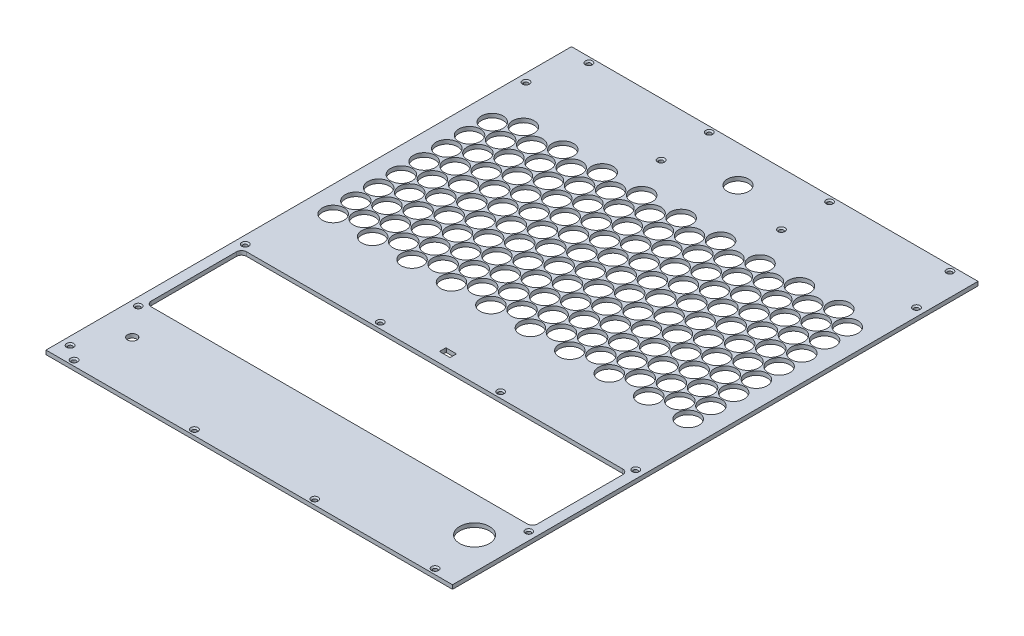
SolidWorks part; units mm, degrees
ref_plane "Ebene vorne" through (0, 0, 0) normal (0, 0, 1) x (1, 0, 0)
ref_plane "Ebene oben" through (0, 0, 0) normal (0, 1, 0) x (1, 0, 0)
ref_plane "Ebene rechts" through (0, 0, 0) normal (1, 0, 0) x (0, 0, -1)
sketch "Skizze1" plane through (0, 0, 0) normal (0, 1, 0) x (1, 0, 0)
  line L1 (-152, 250) -> (152, 250)
  line L2 (-152, 250) -> (-152, -143)
  line L3 (-152, -143) -> (152, -143)
  line L4 (152, 250) -> (152, -143)
  line L5 (-152, 250) -> (152, -143) construction
  line L6 (-152, -143) -> (152, 250) construction
  point P0 (0, 53.5)
  point P6 (0, 0)
extrude "Aufsatz-Linear austragen1" add sketch "Skizze1" along normal blind 3
sketch "Skizze3" plane through (0, 3, 0) normal (0, 1, 0) x (1, 0, 0)
  line L0 (0, 0) -> (0, 250)
  line L1 (152, 250) -> (-152, 250) construction
  circle A0 centre (-146, -131) radius 1.6
  circle A1 centre (-146, -80) radius 1.6
  circle A2 centre (-146, 0) radius 1.6
  circle A3 centre (-146, 210) radius 1.6
  circle A4 centre (-45, 0) radius 1.6
  circle A5 centre (-45, 210) radius 1.6
  circle A6 centre (45, 210) radius 1.6
  circle A7 centre (45, 0) radius 1.6
  circle A8 centre (146, 210) radius 1.6
  circle A9 centre (146, 0) radius 1.6
  circle A10 centre (146, -80) radius 1.6
extrude "PCB-Screws" cut sketch "Skizze3" against normal through all contours A0 | A1 | A2 | A4 | A7 | A9 | A10 | A8 | A6 | A5 | A3 region at (-146, 3, 131) region at (-146, 3, 80) region at (-146, 3, 0) region at (-146, 3, -210) region at (-45, 3, 0) region at (-45, 3, -210) region at (45, 3, -210) region at (45, 3, 0) region at (146, 3, -210) region at (146, 3, 0) region at (146, 3, 80)
sketch "Skizze4" plane through (0, 3, 0) normal (0, 1, 0) x (1, 0, 0)
  circle A0 centre (0, 61) radius 8.075
  circle A1 centre (0, 78) radius 8.075
  circle A2 centre (0, 95) radius 8.075
  circle A3 centre (0, 112) radius 8.075
  circle A4 centre (0, 129) radius 8.075
  circle A5 centre (0, 146) radius 8.075
  circle A6 centre (0, 163) radius 8.075
  circle A7 centre (0, 180) radius 8.075
  circle A8 centre (-14.75, 52.5) radius 8.075
  circle A9 centre (-14.75, 69.5) radius 8.075
  circle A10 centre (-14.75, 86.5) radius 8.075
  circle A11 centre (-14.75, 103.5) radius 8.075
  circle A12 centre (-14.75, 120.5) radius 8.075
  circle A13 centre (-14.75, 137.5) radius 8.075
  circle A14 centre (-14.75, 154.5) radius 8.075
  circle A15 centre (-14.75, 171.5) radius 8.075
  circle A16 centre (-29.5, 61) radius 8.075
  circle A17 centre (-29.5, 78) radius 8.075
  circle A18 centre (-29.5, 95) radius 8.075
  circle A19 centre (-29.5, 112) radius 8.075
  circle A20 centre (-29.5, 129) radius 8.075
  circle A21 centre (-29.5, 146) radius 8.075
  circle A22 centre (-29.5, 163) radius 8.075
  circle A23 centre (-29.5, 180) radius 8.075
  circle A24 centre (-44.25, 52.5) radius 8.075
  circle A25 centre (-44.25, 69.5) radius 8.075
  circle A26 centre (-44.25, 86.5) radius 8.075
  circle A27 centre (-44.25, 103.5) radius 8.075
  circle A28 centre (-44.25, 120.5) radius 8.075
  circle A29 centre (-44.25, 137.5) radius 8.075
  circle A30 centre (-44.25, 154.5) radius 8.075
  circle A31 centre (-44.25, 171.5) radius 8.075
  circle A32 centre (-59, 61) radius 8.075
  circle A33 centre (-59, 78) radius 8.075
  circle A34 centre (-59, 95) radius 8.075
  circle A35 centre (-59, 112) radius 8.075
  circle A36 centre (-59, 129) radius 8.075
  circle A37 centre (-59, 146) radius 8.075
  circle A38 centre (-59, 163) radius 8.075
  circle A39 centre (-59, 180) radius 8.075
  circle A40 centre (-73.75, 52.5) radius 8.075
  circle A41 centre (-73.75, 69.5) radius 8.075
  circle A42 centre (-73.75, 86.5) radius 8.075
  circle A43 centre (-73.75, 103.5) radius 8.075
  circle A44 centre (-73.75, 120.5) radius 8.075
  circle A45 centre (-73.75, 137.5) radius 8.075
  circle A46 centre (-73.75, 154.5) radius 8.075
  circle A47 centre (-73.75, 171.5) radius 8.075
  circle A48 centre (-88.5, 61) radius 8.075
  circle A49 centre (-88.5, 78) radius 8.075
  circle A50 centre (-88.5, 95) radius 8.075
  circle A51 centre (-88.5, 112) radius 8.075
  circle A52 centre (-88.5, 129) radius 8.075
  circle A53 centre (-88.5, 146) radius 8.075
  circle A54 centre (-88.5, 163) radius 8.075
  circle A55 centre (-88.5, 180) radius 8.075
  circle A56 centre (-103.25, 52.5) radius 8.075
  circle A57 centre (-103.25, 69.5) radius 8.075
  circle A58 centre (-103.25, 86.5) radius 8.075
  circle A59 centre (-103.25, 103.5) radius 8.075
  circle A60 centre (-103.25, 120.5) radius 8.075
  circle A61 centre (-103.25, 137.5) radius 8.075
  circle A62 centre (-103.25, 154.5) radius 8.075
  circle A63 centre (-103.25, 171.5) radius 8.075
  circle A64 centre (-118, 61) radius 8.075
  circle A65 centre (-118, 78) radius 8.075
  circle A66 centre (-118, 95) radius 8.075
  circle A67 centre (-118, 112) radius 8.075
  circle A68 centre (-118, 129) radius 8.075
  circle A69 centre (-118, 146) radius 8.075
  circle A70 centre (-118, 163) radius 8.075
  circle A71 centre (-118, 180) radius 8.075
  circle A72 centre (-132.75, 52.5) radius 8.075
  circle A73 centre (-132.75, 69.5) radius 8.075
  circle A74 centre (-132.75, 86.5) radius 8.075
  circle A75 centre (-132.75, 103.5) radius 8.075
  circle A76 centre (-132.75, 120.5) radius 8.075
  circle A77 centre (-132.75, 137.5) radius 8.075
  circle A78 centre (-132.75, 154.5) radius 8.075
  circle A79 centre (-132.75, 171.5) radius 8.075
  circle A80 centre (29.5, 61) radius 8.075
  circle A81 centre (29.5, 78) radius 8.075
  circle A82 centre (29.5, 95) radius 8.075
  circle A83 centre (29.5, 112) radius 8.075
  circle A84 centre (29.5, 129) radius 8.075
  circle A85 centre (29.5, 146) radius 8.075
  circle A86 centre (29.5, 163) radius 8.075
  circle A87 centre (29.5, 180) radius 8.075
  circle A88 centre (14.75, 52.5) radius 8.075
  circle A89 centre (14.75, 69.5) radius 8.075
  circle A90 centre (14.75, 86.5) radius 8.075
  circle A91 centre (14.75, 103.5) radius 8.075
  circle A92 centre (14.75, 120.5) radius 8.075
  circle A93 centre (14.75, 137.5) radius 8.075
  circle A94 centre (14.75, 154.5) radius 8.075
  circle A95 centre (14.75, 171.5) radius 8.075
  circle A96 centre (59, 61) radius 8.075
  circle A97 centre (59, 78) radius 8.075
  circle A98 centre (59, 95) radius 8.075
  circle A99 centre (59, 112) radius 8.075
  circle A100 centre (59, 129) radius 8.075
  circle A101 centre (59, 146) radius 8.075
  circle A102 centre (59, 163) radius 8.075
  circle A103 centre (59, 180) radius 8.075
  circle A104 centre (44.25, 52.5) radius 8.075
  circle A105 centre (44.25, 69.5) radius 8.075
  circle A106 centre (44.25, 86.5) radius 8.075
  circle A107 centre (44.25, 103.5) radius 8.075
  circle A108 centre (44.25, 120.5) radius 8.075
  circle A109 centre (44.25, 137.5) radius 8.075
  circle A110 centre (44.25, 154.5) radius 8.075
  circle A111 centre (44.25, 171.5) radius 8.075
  circle A112 centre (88.5, 61) radius 8.075
  circle A113 centre (88.5, 78) radius 8.075
  circle A114 centre (88.5, 95) radius 8.075
  circle A115 centre (88.5, 112) radius 8.075
  circle A116 centre (88.5, 129) radius 8.075
  circle A117 centre (88.5, 146) radius 8.075
  circle A118 centre (88.5, 163) radius 8.075
  circle A119 centre (88.5, 180) radius 8.075
  circle A120 centre (73.75, 52.5) radius 8.075
  circle A121 centre (73.75, 69.5) radius 8.075
  circle A122 centre (73.75, 86.5) radius 8.075
  circle A123 centre (73.75, 103.5) radius 8.075
  circle A124 centre (73.75, 120.5) radius 8.075
  circle A125 centre (73.75, 137.5) radius 8.075
  circle A126 centre (73.75, 154.5) radius 8.075
  circle A127 centre (73.75, 171.5) radius 8.075
  circle A128 centre (118, 61) radius 8.075
  circle A129 centre (118, 78) radius 8.075
  circle A130 centre (118, 95) radius 8.075
  circle A131 centre (118, 112) radius 8.075
  circle A132 centre (118, 129) radius 8.075
  circle A133 centre (118, 146) radius 8.075
  circle A134 centre (118, 163) radius 8.075
  circle A135 centre (118, 180) radius 8.075
  circle A136 centre (103.25, 52.5) radius 8.075
  circle A137 centre (103.25, 69.5) radius 8.075
  circle A138 centre (103.25, 86.5) radius 8.075
  circle A139 centre (103.25, 103.5) radius 8.075
  circle A140 centre (103.25, 120.5) radius 8.075
  circle A141 centre (103.25, 137.5) radius 8.075
  circle A142 centre (103.25, 154.5) radius 8.075
  circle A143 centre (103.25, 171.5) radius 8.075
  circle A152 centre (132.75, 52.5) radius 8.075
  circle A153 centre (132.75, 69.5) radius 8.075
  circle A154 centre (132.75, 86.5) radius 8.075
  circle A155 centre (132.75, 103.5) radius 8.075
  circle A156 centre (132.75, 120.5) radius 8.075
  circle A157 centre (132.75, 137.5) radius 8.075
  circle A158 centre (132.75, 154.5) radius 8.075
  circle A159 centre (132.75, 171.5) radius 8.075
  circle A160 centre (147.5, 61) radius 8.075 [skipped]
  circle A161 centre (147.5, 78) radius 8.075 [skipped]
  circle A162 centre (147.5, 95) radius 8.075 [skipped]
  circle A163 centre (147.5, 112) radius 8.075 [skipped]
  circle A164 centre (147.5, 129) radius 8.075 [skipped]
  circle A165 centre (147.5, 146) radius 8.075 [skipped]
  circle A166 centre (147.5, 163) radius 8.075 [skipped]
  circle A167 centre (147.5, 180) radius 8.075 [skipped]
  dimension "D1" = 8
  dimension "D2" = 8
extrude "Transducers" cut sketch "Skizze4" against normal through all
sketch "Skizze5" plane through (0, 3, 0) normal (0, 1, 0) x (1, 0, 0)
  line L0 (-3.45, 8.02) -> (3.45, 8.02)
  line L1 (-3.2, 7.27) -> (3.2, 7.27)
  line L2 (-3.2, 7.27) -> (-3.2, 3.97)
  line L3 (-3.2, 3.97) -> (3.2, 3.97)
  line L4 (3.2, 7.27) -> (3.2, 3.97)
  line L5 (-3.2, 7.27) -> (3.2, 3.97) construction
  line L6 (-3.2, 3.97) -> (3.2, 7.27) construction
  line L7 (3.95, 7.52) -> (3.95, 3.72)
  line L8 (-3.45, 3.22) -> (3.45, 3.22)
  line L9 (-3.95, 7.52) -> (-3.95, 3.72)
  line L10 (-3.95, 8.02) -> (3.95, 8.02) construction
  line L11 (3.95, 8.02) -> (3.95, 3.22) construction
  line L12 (-3.95, 3.22) -> (3.95, 3.22) construction
  line L13 (-3.95, 8.02) -> (-3.95, 3.22) construction
  arc A0 (3.45, 8.02) -> (3.95, 7.52) centre (3.45, 7.52) cw
  arc A1 (3.95, 3.72) -> (3.45, 3.22) centre (3.45, 3.72) cw
  arc A2 (-3.45, 3.22) -> (-3.95, 3.72) centre (-3.45, 3.72) cw
  arc A3 (-3.45, 8.02) -> (-3.95, 7.52) centre (-3.45, 7.52) ccw
  point P0 (0, 5.62)
  point P5 (0, 0)
  point P6 (0, 0)
  dimension "D2" = 0.5
  dimension "D1" = 0.75
extrude "ToF-Sensor" cut sketch "Skizze5" against normal through all contours L0 A3 L9 A2 L8 A1 L7 A0 L1 L4 L3 L2 | L4 L1 L2 L3 region at (0, 3, -7.9276) region at (0, 3, -5.62)
sketch "Skizze6" plane through (0, 3, 0) normal (0, 1, 0) x (1, 0, 0)
  line L0 (-144.4, -8.1) -> (-144.4, -71.9)
  line L1 (-140.65, -5.1) -> (140.65, -5.1)
  line L2 (-143.65, -8.1) -> (-143.65, -71.9)
  line L3 (-140.65, -74.9) -> (140.65, -74.9)
  line L4 (143.65, -8.1) -> (143.65, -71.9)
  line L5 (-143.65, -5.1) -> (143.65, -74.9) construction
  line L6 (-143.65, -74.9) -> (143.65, -5.1) construction
  line L7 (-140.65, -75.65) -> (140.65, -75.65)
  line L8 (144.4, -8.1) -> (144.4, -71.9)
  line L9 (-140.65, -4.35) -> (140.65, -4.35)
  arc A0 (140.65, -74.9) -> (143.65, -71.9) centre (140.65, -71.9) ccw
  arc A1 (-143.65, -71.9) -> (-140.65, -74.9) centre (-140.65, -71.9) ccw
  arc A2 (-140.65, -5.1) -> (-143.65, -8.1) centre (-140.65, -8.1) ccw
  arc A3 (140.65, -5.1) -> (143.65, -8.1) centre (140.65, -8.1) cw
  arc A4 (-144.4, -71.9) -> (-140.65, -75.65) centre (-140.65, -71.9) ccw
  arc A5 (140.65, -75.65) -> (144.4, -71.9) centre (140.65, -71.9) ccw
  arc A6 (140.65, -4.35) -> (144.4, -8.1) centre (140.65, -8.1) cw
  arc A7 (-140.65, -4.35) -> (-144.4, -8.1) centre (-140.65, -8.1) ccw
  point P0 (0, -40)
  point P5 (0, 0)
  dimension "D1" = 3
  dimension "D2" = 0.75
extrude "Display" cut sketch "Skizze6" against normal through all contours L9 A7 L0 A4 L7 A5 L8 A6 L1 A3 L4 A0 L3 A1 L2 A2 | A3 L1 A2 L2 A1 L3 A0 L4 region at (-143.0913, 3, 5.6587) region at (0, 3, 40)
sketch "Skizze7" plane through (0, 3, 0) normal (0, 1, 0) x (1, 0, 0)
  circle A0 centre (0, 222.5) radius 8
extrude "Camera" cut sketch "Skizze7" against normal through all
sketch "Skizze9" plane through (0, 3, 0) normal (0, 1, 0) x (1, 0, 0)
  circle A0 centre (-128, -102.5) radius 3.5
extrude "Rotary Encoder" cut sketch "Skizze9" against normal through all
sketch "Skizze10" plane through (0, 3, 0) normal (0, 1, 0) x (1, 0, 0)
  circle A0 centre (128, -102.5) radius 11.1
  point P2 (0, 0)
extrude "RGB-Button" cut sketch "Skizze10" against normal through all
sketch "Skizze8" plane through (0, 3, 0) normal (0, 1, 0) x (1, 0, 0)
  line L0 (152, -143) -> (152, 250) construction
  line L1 (-152, -143) -> (152, -143)
  line L2 (-152, -143) -> (-152, -135)
  line L3 (-152, -135) -> (152, -135)
  line L5 (-152, 53.5) -> (152, 53.5)
  line L10 (-152, 250) -> (-152, -143) construction
  line L11 (0, -135) -> (0, -143)
  circle A0 centre (-135, -139) radius 1.6
  circle A2 centre (-45, -139) radius 1.6
  circle A3 centre (45, -139) radius 1.6
  circle A4 centre (135, -139) radius 1.6
  circle A5 centre (135, 246) radius 1.6
  circle A6 centre (45, 246) radius 1.6
  circle A7 centre (-45, 246) radius 1.6
  circle A8 centre (-135, 246) radius 1.6
extrude "Main-Screws" cut sketch "Skizze8" against normal through all contours A8 | A7 | A6 | A5 | A0 | A2 | A3 | A4 region at (-135, 3, 139) region at (-45, 3, 139) region at (45, 3, 139) region at (135, 3, 139) region at (135, 3, -246) region at (45, 3, -246) region at (-45, 3, -246) region at (-135, 3, -246)
chamfer "Fase1" distance 1 angle 45 19 edges at (135, 3, -244.4) (146, 3, -208.4) (45, 3, -244.4) (45, 3, -208.4) (-45, 3, -244.4) (-45, 3, -208.4) (-135, 3, -244.4) (-146, 3, -208.4) (146, 3, 1.6) (45, 3, 1.6) (-45, 3, 1.6) (-146, 3, 1.6) (146, 3, 81.6) (135, 3, 140.6) (45, 3, 140.6) (-45, 3, 140.6) (-146, 3, 81.6) (-135, 3, 140.6) (-146, 3, 132.6)
